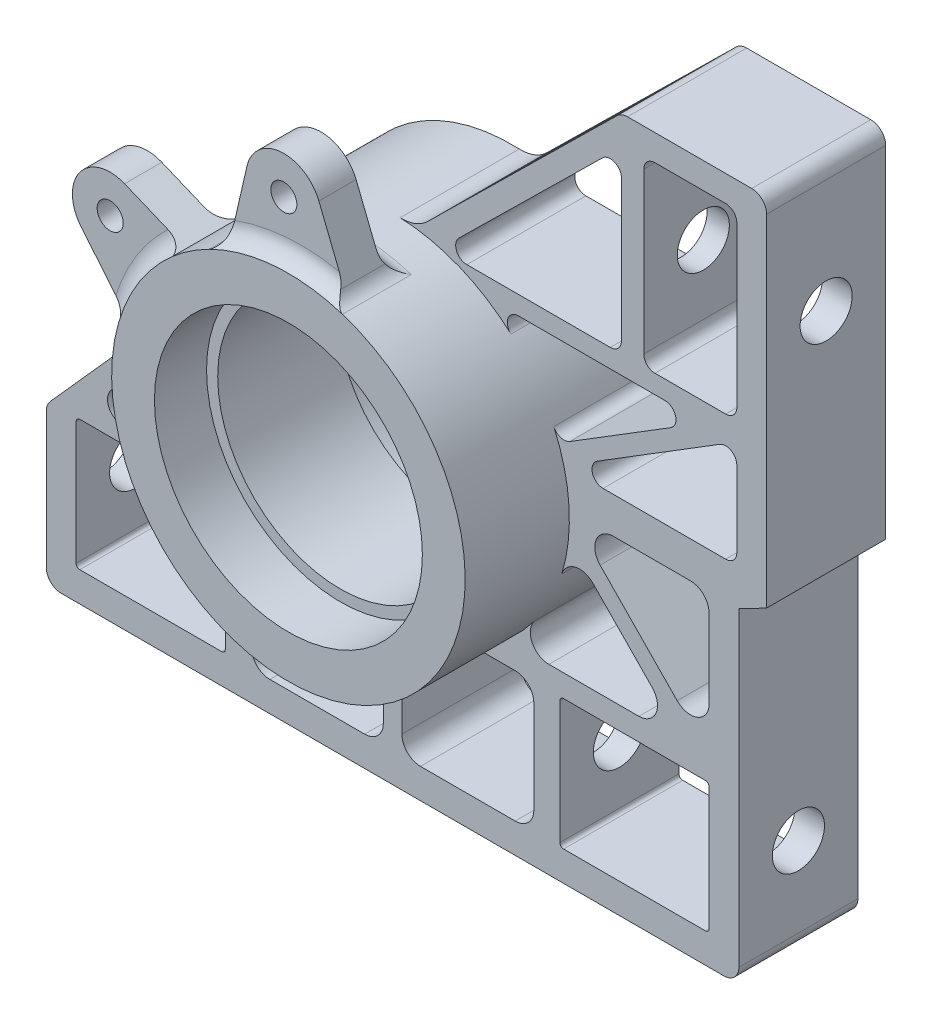
SolidWorks part; units mm, degrees
material "7075-T6 (SN)"
ref_plane "Front Plane" through (0, 0, 0) normal (0, 0, 1) x (1, 0, 0)
ref_plane "Top Plane" through (0, 0, 0) normal (0, 1, 0) x (1, 0, 0)
ref_plane "Right Plane" through (0, 0, 0) normal (1, 0, 0) x (0, 0, -1)
sketch "Sketch1" plane through (0, 0, 0) normal (0, 0, 1) x (1, 0, 0)
  circle A0 centre (0, 0) radius 36
  circle A1 centre (0, 0) radius 47.5
  dimension "D1" = 72
  dimension "D2" = 95
extrude "Boss-Extrude1" add sketch "Sketch1" along normal blind 60
sketch "Sketch2" plane through (0, 0, 0) normal (0, 0, -1) x (-1, 0, 0)
  line L0 (0, 0) -> (0, -85.5) construction
  line L1 (-89.05, -85.5) -> (89.05, -85.5)
  line L2 (93.05, -81.5) -> (93.05, -45.0252)
  line L4 (-63.1377, 101.5) -> (-96.5, 101.5)
  line L6 (-65, -60) -> (65, -60) construction
  line L7 (-65, -60) -> (-65, 70) construction
  line L8 (-65, 70) -> (-80, 70) construction
  line L9 (-84.05, -77.5) -> (-45.95, -77.5)
  line L10 (-85.05, -76.5) -> (-85.05, -43.5)
  line L11 (-84.05, -42.5) -> (-45.95, -42.5)
  line L12 (-44.95, -76.5) -> (-44.95, -43.5)
  line L13 (-85.05, -77.5) -> (-44.95, -42.5) construction
  line L14 (-85.05, -42.5) -> (-44.95, -77.5) construction
  line L15 (45.95, -77.5) -> (84.05, -77.5)
  line L16 (44.95, -76.5) -> (44.95, -43.5)
  line L17 (45.95, -42.5) -> (84.05, -42.5)
  line L18 (85.05, -76.5) -> (85.05, -43.5)
  line L19 (44.95, -77.5) -> (85.05, -42.5) construction
  line L20 (44.95, -42.5) -> (85.05, -77.5) construction
  line L25 (-100.5, 97.5) -> (-100.5, 5.8481)
  line L26 (-89.5, 94.5) -> (-70.5, 94.5)
  line L27 (-92.5, 91.5) -> (-92.5, 48.5)
  line L28 (-89.5, 45.5) -> (-70.5, 45.5)
  line L29 (-67.5, 91.5) -> (-67.5, 48.5)
  line L30 (-92.5, 94.5) -> (-67.5, 45.5) construction
  line L31 (-92.5, 45.5) -> (-67.5, 94.5) construction
  line L32 (-93.05, -81.5) -> (-93.05, 1.9641)
  line L33 (-93.05, 1.9641) -> (-100.5, 5.8481)
  line L34 (92.0346, -42.362) -> (46.7544, 8.3829)
  line L35 (-60.3325, 100.3515) -> (-6.1946, 47.0943)
  line L36 (-61.5, 86.425) -> (-61.5, 48.5)
  line L37 (-58.5, 45.5) -> (-19.9478, 45.5)
  line L38 (-17.844, 50.6386) -> (-56.3961, 88.5636)
  line L39 (-92.5, 35.114) -> (-92.5, 14.7271)
  line L40 (-89.5, 11.7271) -> (-56.5736, 11.7271)
  line L41 (-54.9943, 17.2778) -> (-87.9207, 37.6647)
  line L42 (-74.7284, 34.9493) -> (-47.6317, 18.172)
  line L43 (-73.1491, 40.5) -> (-33.8231, 40.5)
  line L44 (-85.05, -3.0359) -> (-85.05, -24.2301)
  line L45 (-76.4741, -27.7248) -> (-55.7612, -6.5306)
  line L46 (-59.3371, 1.9641) -> (-80.05, 1.9641)
  line L47 (-69.757, -28.0053) -> (-53.8273, -11.7055)
  line L60 (-66.1811, -36.5) -> (-42, -36.5)
  line L68 (53.6007, -6.837) -> (75.599, -31.4902)
  line L69 (72.6144, -38.1534) -> (49.95, -38.1534)
  line L71 (44.95, -33.1534) -> (44.95, -15.3541)
  line L72 (-32.95, -77.5) -> (-7.5, -77.5)
  line L73 (-2.5, -72.5) -> (-2.5, -47.4342)
  line L74 (-37.95, -72.5) -> (-37.95, -47.5)
  line L75 (-32.95, -42.5) -> (-21.2132, -42.5)
  line L76 (2.5, -72.5) -> (2.5, -47.4342)
  line L77 (7.5, -77.5) -> (32.9501, -77.5)
  line L78 (37.95, -72.5331) -> (37.95, -28.5665)
  circle A0 centre (0, 0) radius 47.5 construction
  arc A1 (24.8193, 40.5) -> (-44.6143, 16.3038) centre (0, 0) ccw construction
  arc A2 (-31.8138, 35.2723) -> (-43.3166, 19.4916) centre (0, 0) ccw
  arc A3 (-46.0296, 11.7271) -> (-47.4974, 0.497) centre (0, 0) ccw construction
  arc A4 (-45.4656, -13.7526) -> (-38, -28.5) centre (0, 0) ccw
  arc A5 (-47.2398, -4.965) -> (-30.3974, -36.5) centre (0, 0) ccw construction
  circle A7 centre (0, 0) radius 47.5
  arc A9 (7.4649, -46.9098) -> (37.95, -28.5665) centre (0, 0) ccw construction
  arc A10 (44.3531, -17.0017) -> (46.9996, -6.8768) centre (0, 0) ccw
  arc A11 (43.2647, -19.6065) -> (46.6848, -8.7623) centre (0, 0) ccw construction
  arc A12 (-33.8144, -33.3592) -> (-11.3105, -46.1337) centre (0, 0) ccw
  arc A13 (-37.95, -28.5665) -> (-7.4649, -46.9098) centre (0, 0) ccw construction
  arc A16 (-45.95, -77.5) -> (-44.95, -76.5) centre (-45.95, -76.5) ccw
  arc A17 (-84.05, -77.5) -> (-85.05, -76.5) centre (-84.05, -76.5) cw
  arc A18 (-85.05, -43.5) -> (-84.05, -42.5) centre (-84.05, -43.5) cw
  arc A19 (-45.95, -42.5) -> (-44.95, -43.5) centre (-45.95, -43.5) cw
  arc A20 (45.95, -77.5) -> (44.95, -76.5) centre (45.95, -76.5) cw
  arc A21 (84.05, -77.5) -> (85.05, -76.5) centre (84.05, -76.5) ccw
  arc A22 (84.05, -42.5) -> (85.05, -43.5) centre (84.05, -43.5) cw
  arc A23 (44.95, -43.5) -> (45.95, -42.5) centre (45.95, -43.5) cw
  arc A24 (-70.5, 45.5) -> (-67.5, 48.5) centre (-70.5, 48.5) ccw
  arc A25 (-92.5, 48.5) -> (-89.5, 45.5) centre (-89.5, 48.5) ccw
  arc A26 (-89.5, 94.5) -> (-92.5, 91.5) centre (-89.5, 91.5) ccw
  arc A27 (-70.5, 94.5) -> (-67.5, 91.5) centre (-70.5, 91.5) cw
  arc A28 (-19.9478, 45.5) -> (-17.844, 50.6386) centre (-19.9478, 48.5) ccw
  arc A29 (-61.5, 48.5) -> (-58.5, 45.5) centre (-58.5, 48.5) ccw
  arc A30 (-61.5, 86.425) -> (-56.3961, 88.5636) centre (-58.5, 86.425) cw
  arc A31 (-47.6317, 18.172) -> (-43.3166, 19.4916) centre (-46.0524, 20.7226) ccw
  arc A32 (-74.7284, 34.9493) -> (-73.1491, 40.5) centre (-73.1491, 37.5) cw
  arc A33 (-33.8231, 40.5) -> (-31.8138, 35.2723) centre (-33.8231, 37.5) cw
  arc A34 (-92.5, 14.7271) -> (-89.5, 11.7271) centre (-89.5, 14.7271) ccw
  arc A35 (-56.5736, 11.7271) -> (-54.9943, 17.2778) centre (-56.5736, 14.7271) ccw
  arc A36 (-92.5, 35.114) -> (-87.9207, 37.6647) centre (-89.5, 35.114) cw
  arc A37 (-42, -36.5) -> (-38, -28.5) centre (-42, -31.5) ccw
  arc A38 (-53.8273, -11.7055) -> (-45.4656, -13.7526) centre (-50.2514, -15.2002) cw
  arc A39 (-69.757, -28.0053) -> (-66.1811, -36.5) centre (-66.1811, -31.5) ccw
  arc A40 (-85.05, -24.2301) -> (-76.4741, -27.7248) centre (-80.05, -24.2301) ccw
  arc A41 (-55.7612, -6.5306) -> (-59.3371, 1.9641) centre (-59.3371, -3.0359) ccw
  arc A42 (-85.05, -3.0359) -> (-80.05, 1.9641) centre (-80.05, -3.0359) cw
  arc A61 (89.05, -85.5) -> (93.05, -81.5) centre (89.05, -81.5) ccw
  arc A62 (-89.05, -85.5) -> (-93.05, -81.5) centre (-89.05, -81.5) cw
  arc A64 (93.05, -45.0252) -> (92.0346, -42.362) centre (89.05, -45.0252) ccw
  arc A65 (-60.3325, 100.3515) -> (-63.1377, 101.5) centre (-63.1377, 97.5) ccw
  arc A66 (-96.5, 101.5) -> (-100.5, 97.5) centre (-96.5, 97.5) ccw
  arc A67 (49.95, -38.1534) -> (44.95, -33.1534) centre (49.95, -33.1534) cw
  arc A69 (32.9501, -77.5) -> (37.95, -72.5331) centre (32.9501, -72.5) ccw
  arc A70 (2.5, -72.5) -> (7.5, -77.5) centre (7.5, -72.5) ccw
  arc A71 (-7.5, -77.5) -> (-2.5, -72.5) centre (-7.5, -72.5) ccw
  arc A72 (-32.95, -77.5) -> (-37.95, -72.5) centre (-32.95, -72.5) cw
  arc A73 (-37.95, -47.5) -> (-32.95, -42.5) centre (-32.95, -47.5) cw
  arc A74 (53.6007, -6.837) -> (46.6848, -8.7623) centre (50.6162, -9.5002) ccw
  arc A75 (75.599, -31.4902) -> (72.6144, -38.1534) centre (72.6144, -34.1534) cw
  point P6 (0, -85.5)
  point P125 (-92.5, 40.5)
  point P136 (-85.05, -36.5)
  point P139 (-47.4594, 1.9641)
  point P150 (2.5, -77.5)
  point P154 (-2.5, -77.5)
  point P163 (47.5, 0)
  point P164 (85.05, -44.3653)
  point P165 (33.4574, -33.7173)
  point P197 (93.05, -85.5)
  point P203 (93.05, -43.5)
  point P206 (-61.5, 101.5)
  point P209 (-100.5, 101.5)
  dimension "D16" = 95
  dimension "D18" = 5
  dimension "D25" = 1
  dimension "D26" = 1
  dimension "D27" = 3
  dimension "D28" = 3
  dimension "D29" = 3
  dimension "D30" = 3
  dimension "D31" = 5
  dimension "D35" = 4
  dimension "D36" = 4
  dimension "D7" = 7
  dimension "D5" = 7
  dimension "D20" = 47.5
  dimension "D21" = 5
  dimension "D22" = 4
  dimension "D1" = 130
  dimension "D3" = 130
  dimension "D4" = 33
  dimension "D6" = 40.1
  dimension "D8" = 35
  dimension "D9" = 7
  dimension "D10" = 15
  dimension "D11" = 25
  dimension "D12" = 49
  dimension "D13" = 8
  dimension "8" = 8
  dimension "D14" = 8
  dimension "D15" = 39
  dimension "D17" = 73.5289
  dimension "D19" = 6
  dimension "D23" = 42
  dimension "D24" = 0
  dimension "D37" = 5
  dimension "D38" = 5
extrude "Boss-Extrude2" add sketch "Sketch2" against normal blind 32
sketch3d "3DSketch1" plane through (0, 0, 0) normal (0, 0, 1) x (1, 0, 0)
  dimension "D1" = 10
sketch "Sketch3" plane through (0, 0, 50) normal (0, 0, 1) x (1, 0, 0)
  line L0 (-4.7305, 61.146) -> (-51.4002, 33.455) construction
  line L1 (-28.0653, 47.3005) -> (0, 0) construction
  line L2 (4.6933, 64.9164) -> (12.5436, 45.2952)
  line L3 (-4.7305, 61.146) -> (0, 0) construction
  line L4 (-14.622, 63.4221) -> (-19.361, 42.827)
  line L5 (-28.3103, 37.517) -> (-48.6575, 43.2274)
  line L6 (-51.4002, 33.455) -> (0, 0) construction
  line L7 (-45.7664, 10.6975) -> (-59.2255, 26.9908)
  circle A0 centre (0, 0) radius 61.3287 construction
  circle A1 centre (-4.7305, 61.146) radius 3.5
  circle A2 centre (-51.4002, 33.455) radius 3.5
  circle A3 centre (-4.7305, 61.146) radius 10.15
  circle A4 centre (-51.4002, 33.455) radius 10.15
  circle A5 centre (0, 0) radius 47
  point P7 (-28.0653, 47.3005)
  dimension "D1" = 55
  dimension "D2" = 20.3
  dimension "D3" = 7
  dimension "D6" = 20.3
  dimension "D8" = 16
  dimension "D9" = 94
  dimension "D4" = 54.2665
  dimension "D5" = 54.2665
  dimension "D7" = 16
fillet "Fillet4" radius 10 1 edges at (6.1946, 47.0943, 16)
sketch "Sketch4" plane through (100.5, 0, 0) normal (1, 0, 0) x (0, 0, -1)
  line L0 (-16, 94.5) -> (-16, 45.5) construction
  line L2 (-32, 94.5) -> (0, 94.5) construction
  line L3 (-32, 45.5) -> (0, 45.5) construction
  line L4 (-32, 94.5) -> (0, 94.5)
  line L5 (-32, 45.5) -> (0, 45.5)
  circle A1 centre (-16, 67) radius 7
  point P4 (-16, 70)
  dimension "D1" = 14
  dimension "D2" = 3
extrude "Cut-Extrude1" cut sketch "Sketch4" against normal up to surface (39 mm away) contours L0 A1 | A1 L0 up to face at (61.5, 67.4625, 16)
sketch "Sketch5" plane through (93.05, 0, 0) normal (1, 0, 0) x (0, 0, -1)
  line L0 (-32, -77.5) -> (0, -77.5) construction
  line L1 (-32, -42.5) -> (0, -42.5) construction
  line L2 (-32, -77.5) -> (0, -77.5)
  line L3 (-32, -42.5) -> (0, -42.5)
  line L4 (-16, -42.5) -> (-16, -77.5) construction
  circle A0 centre (-16, -60) radius 7
  dimension "D1" = 14
extrude "Cut-Extrude2" cut sketch "Sketch5" against normal blind 64 contours L4 A0 | A0 L4
mirror "Mirror1" about plane through (0, 0, 0) normal (1, 0, 0) of "Cut-Extrude2"
ref_plane "Plane1" through (0, 0, 30) normal (0, 0, -1) x (-1, 0, 0)
sketch "Sketch6" plane through (0, 0, 30) normal (0, 0, -1) x (-1, 0, 0)
  circle A0 centre (0, 0) radius 36
  circle A1 centre (0, 0) radius 33
  dimension "D1" = 66
extrude "Boss-Extrude4" add sketch "Sketch6" along normal blind 16 and the other way blind 16
fillet "Fillet5" radius 4 3 edges at (2.5, -47.4342, 16) (-2.5, -47.4342, 16) (-37.95, -28.5665, 16)
ref_plane "Plane2" through (0, 0, 56.5) normal (0, 0, 1) x (1, 0, 0)
sketch "Sketch8" plane through (0, 0, 56.5) normal (0, 0, 1) x (1, 0, 0)
  line L0 (-4.7302, 61.1433) -> (-51.3974, 33.4542) construction
  line L1 (-28.0638, 47.2988) -> (0, 0) construction
  line L2 (4.6942, 64.914) -> (12.5436, 45.2952)
  line L3 (-4.7302, 61.1433) -> (0, 0) construction
  line L4 (-14.6225, 63.4196) -> (-19.361, 42.827)
  line L6 (-51.3974, 33.4542) -> (0, 0) construction
  line L7 (-45.7661, 10.6988) -> (-59.223, 26.9902)
  line L8 (-30.4779, 35.7784) -> (-48.0729, 43.0634)
  line L9 (-48.0729, 43.0634) -> (-48.6548, 43.2267)
  circle A0 centre (0, 0) radius 61.326 construction
  circle A1 centre (-4.7302, 61.1433) radius 3.5
  circle A2 centre (-51.3974, 33.4542) radius 3.5
  circle A3 centre (-4.7302, 61.1433) radius 10.1508
  circle A4 centre (-51.3974, 33.4542) radius 10.15
  circle A5 centre (0, 0) radius 47
  point P6 (-28.0638, 47.2988)
extrude "Boss-Extrude6" add sketch "Sketch8" against normal blind 10
fillet "Fillet12" radius 5 7 edges at (-3.6638, 47.3585, 46.5) (12.3109, 45.8769, 51.5) (-3.6638, 47.3585, 56.5) (-19.2205, 43.4375, 51.5) (-40.526, 24.7768, 46.5) (-40.526, 24.7768, 56.5) (-46.1651, 11.1819, 51.5)
sketch "Sketch9" plane through (0, 0, 56.5) normal (0, 0, 1) x (1, 0, 0)
  point P0 (-4.7302, 61.1433)
  point P1 (-51.3974, 33.4542)
  point P3 (144.7565, 101.9514)
